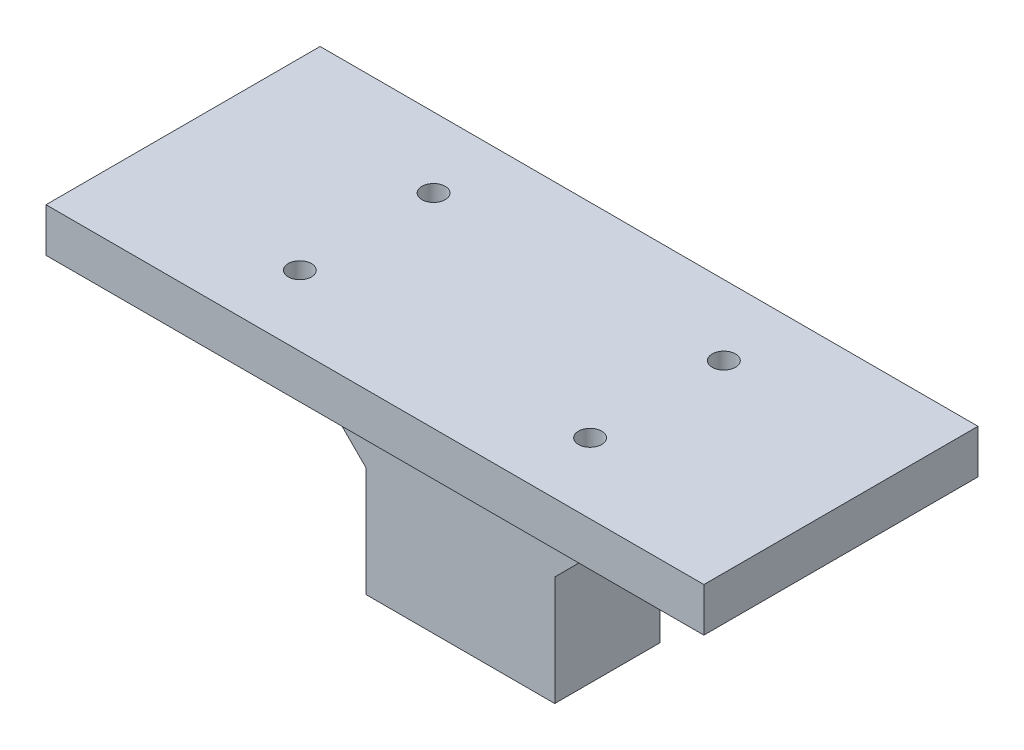
SolidWorks part; units mm, degrees
ref_plane "Front Plane" through (0, 0, 0) normal (0, 0, 1) x (1, 0, 0)
ref_plane "Top Plane" through (0, 0, 0) normal (0, 1, 0) x (1, 0, 0)
ref_plane "Right Plane" through (0, 0, 0) normal (1, 0, 0) x (0, 0, -1)
sketch "Sketch1" plane through (0, 0, 0) normal (0, 1, 0) x (1, 0, 0)
  line L1 (0, 0) -> (150, 0)
  line L2 (0, 0) -> (0, 62.5)
  line L4 (150, 0) -> (150, 62.5)
  line L8 (0, 62.5) -> (51, 62.5)
  line L9 (99, 62.5) -> (150, 62.5)
  line L14 (51, 62.5) -> (99, 62.5)
  circle A0 centre (108.0546, 46.5) radius 2.65
  circle A1 centre (41.8737, 46.5) radius 2.65
  circle A2 centre (41.8737, 16) radius 2.65
  circle A3 centre (108.0546, 16) radius 2.65
  dimension "D9" = 5.3
  dimension "D11" = 5.3
  dimension "D14" = 5.3
  dimension "D15" = 5.3
  dimension "D1" = 62.5
  dimension "D2" = 150
  dimension "D4" = 51
  dimension "D5" = 51
extrude "Boss-Extrude1" add sketch "Sketch1" along normal blind 10 contours L8 L2 L1 L4 L9 region at (75.0003, 0, -31.25)
sketch "Sketch2" plane through (0, 0, 0) normal (0, -1, 0) x (1, 0, 0)
  line L0 (0, 0) -> (150, 0) construction
  line L3 (96.5, -43.5) -> (53.5, -43.5)
  line L7 (53.5, -19.5) -> (53.5, -43.5)
  line L9 (96.5, -19.5) -> (53.5, -19.5)
  line L10 (96.5, -19.5) -> (96.5, -43.5)
  line L11 (96.5, -43.5) -> (53.5, -43.5)
  line L12 (53.5, -19.5) -> (53.5, -43.5)
  point P0 (75, 0)
  dimension "D1" = 43
  dimension "D2" = 24
extrude "Boss-Extrude2" add sketch "Sketch2" along normal blind 50 contours L10 L9 L7 L3 region at (75, 0, -31.5)
chamfer "Chamfer12" distance 25 2 edges at (96.5, 0, -31.5) (53.5, 0, -31.5)
sketch "Sketch11" plane through (0, -50, 0) normal (0, -1, 0) x (1, 0, 0)
  line L0 (55.4537, -21) -> (54.9537, -21)
  line L1 (94.5537, -21) -> (95.0537, -21)
  line L3 (54.9537, -21) -> (95.0537, -21)
  line L4 (55.4537, -21) -> (94.5537, -21)
  line L6 (55.4537, -42) -> (94.5537, -42)
  line L10 (54.9537, -21) -> (54.9537, -42)
  line L11 (54.9537, -42) -> (95.0537, -42)
  line L12 (95.0537, -21) -> (95.0537, -42)
  point P6 (75.0037, -31.5)
  dimension "D1" = 39.1
  dimension "D2" = 21
  dimension "D3" = 0.5
  dimension "D4" = 0.5
extrude "Cut-Extrude3" cut sketch "Sketch11" against normal blind 40 contours L10 L3 L12 L11
sketch "Sketch12" plane through (53.5, 0, 0) normal (-1, 0, 0) x (0, 0, 1)
  line L0 (-43.5, -25) -> (-43.5, 0)
  line L1 (-43.5, 0) -> (-19.5, 0) construction
  line L2 (-43.5, -25) -> (-43.5, 0) construction
  line L3 (-43.5, -25) -> (-62.5, 0)
  line L4 (-43.5, 0) -> (-62.5, 0)
extrude "Boss-Extrude3" add sketch "Sketch12" against normal blind 43
fillet "Fillet1" radius 10 2 edges at (121.5, 0, -31.5) (28.5, 0, -31.5)
fillet "Fillet5" radius 1 4 edges at (53.5, 0, -53) (96.5, 0, -53) (96.5, -12.5, -43.5) (53.5, -12.5, -43.5)
sketch "Sketch14" plane through (0, 0, -43.5) normal (0, 0, -1) x (-1, 0, 0)
  line L0 (-24.3579, 0) -> (-52.5, 0)
  line L1 (-52.5, 0) -> (-52.5, -24)
  line L2 (-52.5, -24) -> (-31.4289, -2.9289) construction
  line L3 (-52.5, 0) -> (-52.5, -24) construction
  line L4 (-52.5, -24) -> (-31.4289, -2.9289)
  line L7 (-97.5, -24) -> (-97.5, 0)
  line L8 (-97.5, 0) -> (-125.6421, 0)
  line L9 (-125.6421, 0) -> (-97.5, 0) construction
  line L10 (-97.5, -24) -> (-118.5711, -2.9289)
  arc A0 (-31.4289, -2.9289) -> (-24.3579, 0) centre (-24.3579, -10) cw
  arc A1 (-118.5711, -2.9289) -> (-125.6421, 0) centre (-125.6421, -10) ccw
extrude "Cut-Extrude4" cut sketch "Sketch14" against normal blind 2
